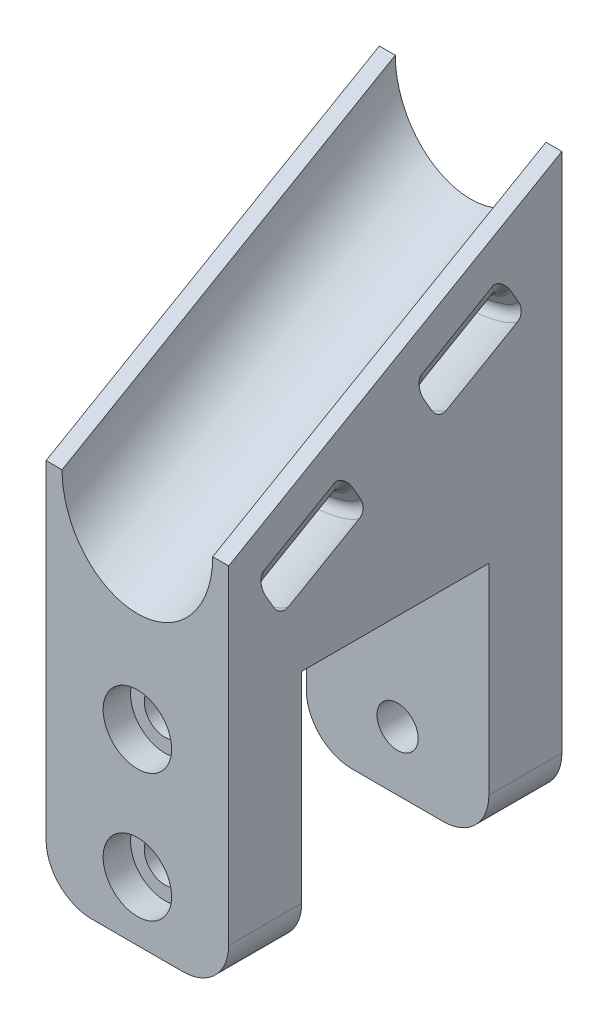
SolidWorks part; units mm, degrees
ref_plane "Спереди" through (0, 0, 0) normal (0, 0, 1) x (1, 0, 0)
ref_plane "Сверху" through (0, 0, 0) normal (0, 1, 0) x (1, 0, 0)
ref_plane "Справа" through (0, 0, 0) normal (1, 0, 0) x (0, 0, -1)
sketch "Эскиз2" plane through (0, 0, 0) normal (1, 0, 0) x (0, 0, -1)
  line L0 (-18.25, -10.5366) -> (18.25, 10.5366)
  line L1 (-10.25, -24.5366) -> (10.25, -24.5366)
  line L2 (-18.25, -10.5366) -> (-18.25, -51.5366)
  line L3 (-18.25, -51.5366) -> (-10.25, -51.5366)
  line L4 (-10.25, -51.5366) -> (-10.25, -24.5366)
  line L5 (18.25, 10.5366) -> (18.25, -51.5366)
  line L6 (18.25, -51.5366) -> (10.25, -51.5366)
  line L7 (10.25, -51.5366) -> (10.25, -24.5366)
  line L8 (0, -14) -> (0, 13.9415) construction
  point P7 (0, -24.5366)
  dimension "D2" = 20.5
  dimension "D3" = 30
  dimension "D4" = 27
  dimension "D5" = 8
  dimension "D1" = 14
extrude "Бобышка-Вытянуть1" add sketch "Эскиз2" along normal mid plane 20
sketch "Эскиз3" plane through (0, 0, 0) normal (0, 0.866, 0.5) x (1, 0, 0)
  line L0 (0, 0) -> (23.477, 0) construction
ref_plane "Плоскость2" through (0, 0, 0) normal (0, -0.5, 0.866) x (1, 0, 0)
sketch "Эскиз4" plane through (0, 0, 0) normal (0, -0.5, 0.866) x (1, 0, 0)
  circle A0 centre (0, 0) radius 8.25
  dimension "D1" = 16.5
extrude "Вырез-Вытянуть1" cut sketch "Эскиз4" against normal through all both and the other way through all
sketch "Эскиз5" plane through (0, 0, 0) normal (0, -0.5, 0.866) x (1, 0, 0)
  line L0 (-10, 0) -> (-10, -4) construction
  line L1 (-10, 0) -> (-10, -35.507) construction
  circle A0 centre (0, 0) radius 10.7703
  circle A1 centre (0, 0) radius 13.7703
  dimension "D1" = 4
  dimension "D2" = 3
extrude "Вырез-Вытянуть2" cut sketch "Эскиз5" against normal blind 11
sketch "Эскиз6" plane through (0, 0, 10.25) normal (0, 0, -1) x (-1, 0, 0)
  line L0 (-10, -38.0366) -> (10, -38.0366) construction
  line L1 (-10, -51.5366) -> (-10, -24.5366) construction
  line L2 (10, -51.5366) -> (10, -24.5366) construction
  circle A0 centre (0, -31.0366) radius 2.25
  circle A1 centre (0, -45.0366) radius 2.25
  point P10 (0, 0)
  dimension "D1" = 4.5
  dimension "D2" = 14
extrude "Вырез-Вытянуть3" cut sketch "Эскиз6" against normal through all
sketch "Эскиз7" plane through (0, 0, 18.25) normal (0, 0, 1) x (1, 0, 0)
  circle A0 centre (0, -31.0366) radius 3.75
  circle A1 centre (0, -45.0366) radius 3.75
  dimension "D1" = 7.5
  dimension "D2" = 7.5
extrude "Вырез-Вытянуть4" cut sketch "Эскиз7" against normal blind 3
fillet "Скругление1" radius 5 4 edges at (10, -51.5366, 14.25) (-10, -51.5366, 14.25) (10, -51.5366, -14.25) (-10, -51.5366, -14.25)
mirror "Зеркальное отражение2" about plane through (0, 0, 0) normal (0, 0, 1) of "Вырез-Вытянуть4", "Вырез-Вытянуть3"
fillet "Скругление2" radius 1 8 edges at (-10, -0.3313, -12.893) (-10, -0.7141, -6.7631) (-10, -5.4486, -9.4966) (0, -3.8274, -14.9114) (0, -6.4255, -16.4114) (-10, -5.8313, -3.3667) (0, -9.3274, -5.3852) (0, -11.9255, -6.8852)
pattern_linear "Линейный массив1" count 2 spacing 20 along (0, -0.5, 0.866) of "Скругление2", "Вырез-Вытянуть2"
equation "\"print_offset\"= 0.5"
equation "\"screw_m5_d\"= 4"
equation "\"screw_m5_hh_d\"= 7"
equation "\"nut_m5_d\"= 7.9"
equation "\"nut_m5_h\"= 3.9"
equation "\"tube_d\"= 16"
equation "\"tube_tape_d\"= 3"
equation "\"tube_tape_h\"= 11"
equation "\"D2@Эскиз2\"=\"print_offset\"+20"
equation "\"D1@Эскиз4\"=\"tube_d\"+\"print_offset\""
equation "\"D2@Эскиз5\"=\"tube_tape_d\""
equation "\"D1@Вырез-Вытянуть2\"=\"tube_tape_h\""
equation "\"D1@Эскиз6\"=\"screw_m5_d\"+\"print_offset\""
equation "\"D1@Эскиз7\"=\"screw_m5_hh_d\"+\"print_offset\""
equation "\"D2@Эскиз7\"=\"D1@Эскиз7\""
